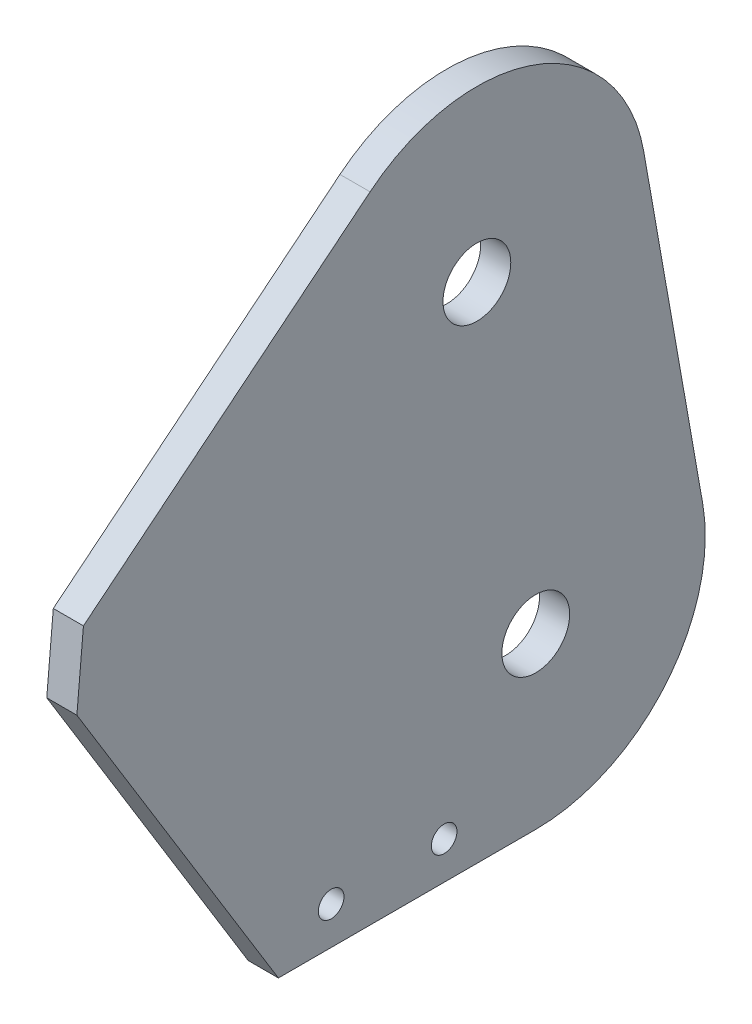
SolidWorks part; units mm, degrees
ref_plane "Front Plane" through (0, 0, 0) normal (0, 0, 1) x (1, 0, 0)
ref_plane "Top Plane" through (0, 0, 0) normal (0, 1, 0) x (1, 0, 0)
ref_plane "Right Plane" through (0, 0, 0) normal (1, 0, 0) x (0, 0, -1)
ref_plane "Plane1" through (-18, 0, 0) normal (-1, 0, 0) x (0, 0, 1)
sketch "Sketch2" plane through (-18, 0, 0) normal (-1, 0, 0) x (0, 0, 1)
  line L0 (48.7484, 82.0825) -> (47.8793, 91.9182) construction
  line L1 (22, 38.5) -> (48.7484, 82.0825) construction
  line L2 (-12.1573, 38.5) -> (22, 38.5) construction
  line L3 (-26.5013, 109.2234) -> (-34.3155, 64.9071) construction
  line L4 (48.7484, 82.0825) -> (47.8793, 91.9182)
  line L5 (-26.5013, 109.2234) -> (-34.3155, 64.9071)
  line L6 (-12.1573, 38.5) -> (22, 38.5)
  line L7 (22, 38.5) -> (48.7484, 82.0825)
  line L8 (48.7484, 82.0825) -> (47.8793, 91.9182)
  line L9 (47.8793, 91.9182) -> (9.8336, 122.7883)
  line L10 (-26.5013, 109.2234) -> (-34.3155, 64.9071)
  line L11 (-12.1573, 38.5) -> (22, 38.5)
  line L12 (22, 38.5) -> (48.7484, 82.0825)
  line L13 (48.7484, 82.0825) -> (47.8793, 91.9182)
  line L14 (47.8793, 91.9182) -> (9.8336, 122.7883)
  line L15 (22, 38.5) -> (48.7484, 82.0825)
  line L16 (-12.1573, 38.5) -> (22, 38.5)
  line L17 (-26.5013, 109.2234) -> (-34.3155, 64.9071)
  circle A0 centre (-12.1573, 61) radius 22.5 construction
  circle A1 centre (-4.3431, 105.3163) radius 22.5 construction
  arc A2 (9.8336, 122.7883) -> (-26.5013, 109.2234) centre (-4.3431, 105.3163) ccw
  arc A3 (-34.3155, 64.9071) -> (-12.1573, 38.5) centre (-12.1573, 61) ccw
  arc A4 (9.8336, 122.7883) -> (-26.5013, 109.2234) centre (-4.3431, 105.3163) ccw
  arc A5 (-34.3155, 64.9071) -> (-12.1573, 38.5) centre (-12.1573, 61) ccw
  arc A6 (-34.3155, 64.9071) -> (-12.1573, 38.5) centre (-12.1573, 61) ccw
  arc A7 (9.8336, 122.7883) -> (-26.5013, 109.2234) centre (-4.3431, 105.3163) ccw
  dimension "D1" = 0
extrude "Boss-Extrude1" add sketch "Sketch2" along normal blind 4 contours L10 A5 L11 L12 L4 L14 A4 region at (-18, 80.1114, 3.1564)
hole_wizard "Hole1" positions "Sketch3" profile "Sketch4" legacy end condition through all
sketch "Sketch3" plane through (-18, 0, 0) normal (1, 0, 0) x (0, 0, -1)
  point P0 (4.3431, 105.3163)
  point P3 (12.1573, 61)
sketch "Sketch4" plane through (-18, 105.3163, -4.3431) normal (0, 1, 0) x (0, 0, -1)
  line L0 (0, 0) -> (0, 4)
  line L1 (0, 4) -> (4.5, 4)
  line L2 (4.5, 4) -> (4.5, 0)
  line L3 (4.5, 0) -> (0, 0)
  line L4 (0, 110) -> (0, -10) construction
  dimension "Diameter" = 9
  dimension "Depth" = 4
hole_wizard "M3 Clearance Hole1" positions "Sketch5" profile "Sketch6" hole size "M3" standard "ANSI Metric" end condition through all
sketch "Sketch5" plane through (-22, 0, 0) normal (-1, 0, 0) x (0, 0, 1)
  point P0 (15, 43.5)
  point P3 (0, 43.5)
sketch "Sketch6" plane through (-22, 43.5, 15) normal (0, 1, 0) x (0, 0, 1)
  line L0 (0, 0) -> (0, 4)
  line L1 (0, 4) -> (1.7, 4)
  line L2 (1.7, 4) -> (1.7, 0.025)
  line L3 (1.7, 0.025) -> (1.725, 0)
  line L5 (1.725, 0) -> (0, 0)
  line L6 (-1.7, 0.025) -> (-1.725, 0) construction
  line L11 (0, -6.35) -> (0, 107.95) construction
  dimension "Thru Hole Dia." = 3.4
  dimension "Thru Hole Depth" = 4
  dimension "Near C'Sink Dia." = 3.45
  dimension "Near C'Sink Angle" = 90
